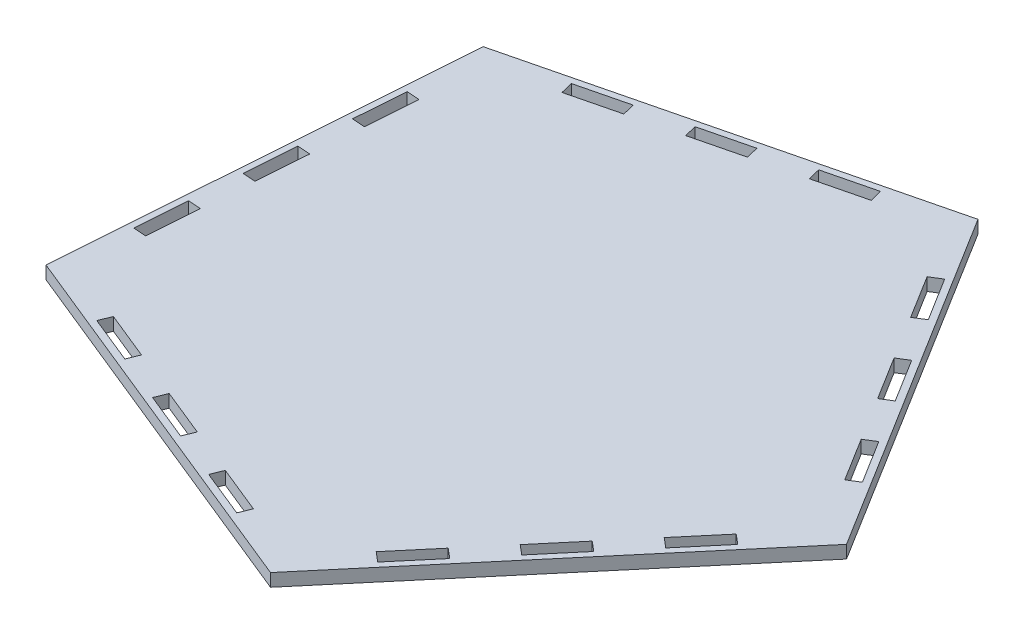
SolidWorks part; units mm, degrees
ref_plane "Front Plane" through (0, 0, 0) normal (0, 0, 1) x (1, 0, 0)
ref_plane "Top Plane" through (0, 0, 0) normal (0, 1, 0) x (1, 0, 0)
ref_plane "Right Plane" through (0, 0, 0) normal (1, 0, 0) x (0, 0, -1)
sketch "Sketch1" plane through (0, 0, 0) normal (0, 1, 0) x (1, 0, 0)
  line L1 (-472.7621, -38.6016) -> (-579.997, 133.9989)
  line L2 (-579.997, 133.9989) -> (-777.2872, 85.3489)
  line L3 (-777.2872, 85.3489) -> (-791.9844, -117.3188)
  line L4 (-791.9844, -117.3188) -> (-603.7775, -193.9245)
  line L5 (-603.7775, -193.9245) -> (-472.7621, -38.6016)
  circle A0 centre (-645.1616, -26.0994) radius 139.8404 construction
  dimension "D1" = 203.2
extrude "Boss-Extrude1" add sketch "Sketch1" along normal blind 6.35
sketch "Sketch2" plane through (0, 6.35, 0) normal (0, 1, 0) x (1, 0, 0)
  line L1 (-659.0013, -161.163) -> (-635.4754, -170.7387)
  line L2 (-659.0013, -161.163) -> (-661.3952, -167.0445)
  line L3 (-661.3952, -167.0445) -> (-637.8693, -176.6202)
  line L4 (-635.4754, -170.7387) -> (-637.8693, -176.6202)
  line L5 (-706.053, -142.0116) -> (-682.5271, -151.5873)
  line L6 (-791.9844, -117.3188) -> (-603.7775, -193.9245) construction
  line L7 (-753.0539, -122.7353) -> (-729.528, -132.311)
  line L8 (-753.0539, -122.7353) -> (-755.4478, -128.6168)
  line L9 (-755.4478, -128.6168) -> (-731.9219, -138.1925)
  line L10 (-729.528, -132.311) -> (-731.9219, -138.1925)
  line L11 (-706.053, -142.0116) -> (-708.4469, -147.8931)
  line L12 (-708.4469, -147.8931) -> (-684.921, -157.4688)
  line L13 (-682.5271, -151.5873) -> (-684.921, -157.4688)
  dimension "D1" = 3.175
  dimension "D2" = 6.35
  dimension "D3" = 25.4
  dimension "D4" = 38.1
  dimension "D5" = 25.4
  dimension "D6" = 6.35
  dimension "D7" = 38.1
  dimension "D8" = 3.175
  dimension "D9" = 6.35
  dimension "D10" = 25.4
  dimension "D11" = 25.4
extrude "Cut-Extrude1" cut sketch "Sketch2" against normal through all
sketch "Sketch4" plane through (0, 6.35, 0) normal (0, 1, 0) x (1, 0, 0)
  line L0 (-603.7775, -193.9245) -> (-472.7621, -38.6016) construction
  line L1 (-570.116, -139.2447) -> (-565.2621, -143.339)
  line L2 (-570.116, -139.2447) -> (-586.4929, -158.6601)
  line L3 (-586.4929, -158.6601) -> (-581.639, -162.7543)
  line L4 (-565.2621, -143.339) -> (-581.639, -162.7543)
  line L6 (-520.9852, -80.9987) -> (-516.1313, -85.0929)
  line L7 (-520.9852, -80.9987) -> (-504.6082, -61.5833)
  line L8 (-504.6082, -61.5833) -> (-499.7544, -65.6775)
  line L9 (-516.1313, -85.0929) -> (-499.7544, -65.6775)
  line L10 (-548.8852, -123.9236) -> (-532.5083, -104.5082)
  line L11 (-548.8852, -123.9236) -> (-553.739, -119.8294)
  line L12 (-553.739, -119.8294) -> (-537.3621, -100.414)
  line L13 (-532.5083, -104.5082) -> (-537.3621, -100.414)
  dimension "D1" = 6.35
  dimension "D2" = 25.4
  dimension "D3" = 3.175
  dimension "D4" = 38.1
  dimension "D5" = 3.175
  dimension "D6" = 6.35
  dimension "D7" = 25.4
  dimension "D8" = 38.1
  dimension "D9" = 6.35
  dimension "D10" = 25.4
  dimension "D11" = 3.175
  dimension "D12" = 25.4
extrude "Cut-Extrude2" cut sketch "Sketch4" against normal through all
sketch "Sketch5" plane through (0, 6.35, 0) normal (0, 1, 0) x (1, 0, 0)
  line L0 (-777.2872, 85.3489) -> (-791.9844, -117.3188) construction
  line L1 (-777.8914, -54.6741) -> (-784.2248, -54.2148)
  line L2 (-777.8914, -54.6741) -> (-779.7286, -80.0076)
  line L3 (-779.7286, -80.0076) -> (-786.0619, -79.5483)
  line L4 (-784.2248, -54.2148) -> (-786.0619, -79.5483)
  line L6 (-774.2171, -4.0071) -> (-780.5505, -3.5479)
  line L7 (-774.2171, -4.0071) -> (-776.0543, -29.3406)
  line L8 (-776.0543, -29.3406) -> (-782.3876, -28.8813)
  line L9 (-780.5505, -3.5479) -> (-782.3876, -28.8813)
  line L10 (-776.8762, 47.1191) -> (-770.5428, 46.6598)
  line L11 (-776.8762, 47.1191) -> (-778.7133, 21.7856)
  line L12 (-778.7133, 21.7856) -> (-772.38, 21.3263)
  line L13 (-770.5428, 46.6598) -> (-772.38, 21.3263)
  dimension "D1" = 6.35
  dimension "D2" = 25.4
  dimension "D3" = 3.175
  dimension "D4" = 38.1
  dimension "D5" = 25.4
  dimension "D6" = 6.35
  dimension "D7" = 3.175
  dimension "D8" = 25.4
  dimension "D9" = 6.35
  dimension "D10" = 25.4
  dimension "D11" = 3.175
  dimension "D12" = 38.1
extrude "Cut-Extrude3" cut sketch "Sketch5" against normal through all
sketch "Sketch6" plane through (0, 6.35, 0) normal (0, 1, 0) x (1, 0, 0)
  line L0 (-472.7621, -38.6016) -> (-579.997, 133.9989) construction
  line L1 (-508.9699, 13.6605) -> (-495.5655, -7.9146)
  line L2 (-508.9699, 13.6605) -> (-514.3636, 10.3094)
  line L3 (-514.3636, 10.3094) -> (-500.9593, -11.2656)
  line L4 (-495.5655, -7.9146) -> (-500.9593, -11.2656)
  line L6 (-522.3742, 35.2356) -> (-527.768, 31.8845)
  line L7 (-522.3742, 35.2356) -> (-535.7786, 56.8106)
  line L8 (-535.7786, 56.8106) -> (-541.1724, 53.4595)
  line L9 (-527.768, 31.8845) -> (-541.1724, 53.4595)
  line L10 (-549.1398, 78.4125) -> (-554.5336, 75.0614)
  line L11 (-549.1398, 78.4125) -> (-562.5442, 99.9876)
  line L12 (-562.5442, 99.9876) -> (-567.9379, 96.6365)
  line L13 (-554.5336, 75.0614) -> (-567.9379, 96.6365)
  dimension "D1" = 6.35
  dimension "D2" = 25.4
  dimension "D3" = 3.175
  dimension "D4" = 38.1
  dimension "D5" = 6.35
  dimension "D6" = 25.4
  dimension "D7" = 3.175
  dimension "D8" = 25.4
  dimension "D9" = 25.4
  dimension "D10" = 6.35
  dimension "D11" = 3.1242
  dimension "D12" = 38.1
extrude "Cut-Extrude4" cut sketch "Sketch6" against normal through all
sketch "Sketch7" plane through (0, 6.35, 0) normal (0, 1, 0) x (1, 0, 0)
  line L0 (-579.997, 133.9989) -> (-777.2872, 85.3489) construction
  line L1 (-614.7084, 115.629) -> (-639.3697, 109.5478)
  line L2 (-614.7084, 115.629) -> (-616.2287, 121.7944)
  line L3 (-616.2287, 121.7944) -> (-640.89, 115.7131)
  line L4 (-639.3697, 109.5478) -> (-640.89, 115.7131)
  line L6 (-665.5513, 109.6319) -> (-690.2125, 103.5506)
  line L7 (-665.5513, 109.6319) -> (-664.031, 103.4666)
  line L8 (-664.031, 103.4666) -> (-688.6922, 97.3853)
  line L9 (-690.2125, 103.5506) -> (-688.6922, 97.3853)
  line L10 (-714.8738, 97.4694) -> (-739.5351, 91.3882)
  line L11 (-714.8738, 97.4694) -> (-713.3535, 91.3041)
  line L12 (-713.3535, 91.3041) -> (-738.0148, 85.2228)
  line L13 (-739.5351, 91.3882) -> (-738.0148, 85.2228)
  point P7 (-615.4686, 118.7117)
  dimension "D1" = 25.4
  dimension "D2" = 6.35
  dimension "D3" = 3.175
  dimension "D4" = 38.1
  dimension "D5" = 6.35
  dimension "D6" = 25.4
  dimension "D7" = 3.175
  dimension "D8" = 25.4
  dimension "D9" = 25.4
  dimension "D10" = 6.35
  dimension "D11" = 3.175
  dimension "D12" = 25.4
extrude "Cut-Extrude5" cut sketch "Sketch7" against normal through all
sketch "Sketch9" plane through (0, 6.35, 0) normal (0, 1, 0) x (1, 0, 0)
  line L0 (-532.6723, -56.7014) -> (-599.8476, -136.3398) construction
  line L1 (-603.7775, -193.9245) -> (-472.7621, -38.6016) construction
  line L2 (-472.7621, -38.6016) -> (-784.6358, -15.9849) construction
  line L3 (-678.6421, 109.6739) -> (-603.7775, -193.9245) construction
  line L4 (-579.997, 133.9989) -> (-777.2872, 85.3489) construction
  line L5 (-777.2872, 85.3489) -> (-791.9844, -117.3188) construction
  circle A0 centre (-599.8476, -136.3398) radius 5.5303
  circle A1 centre (-566.26, -96.5206) radius 5.5742
  circle A2 centre (-532.6723, -56.7014) radius 5.5742
  point P21 (-645.1616, -26.0994)
